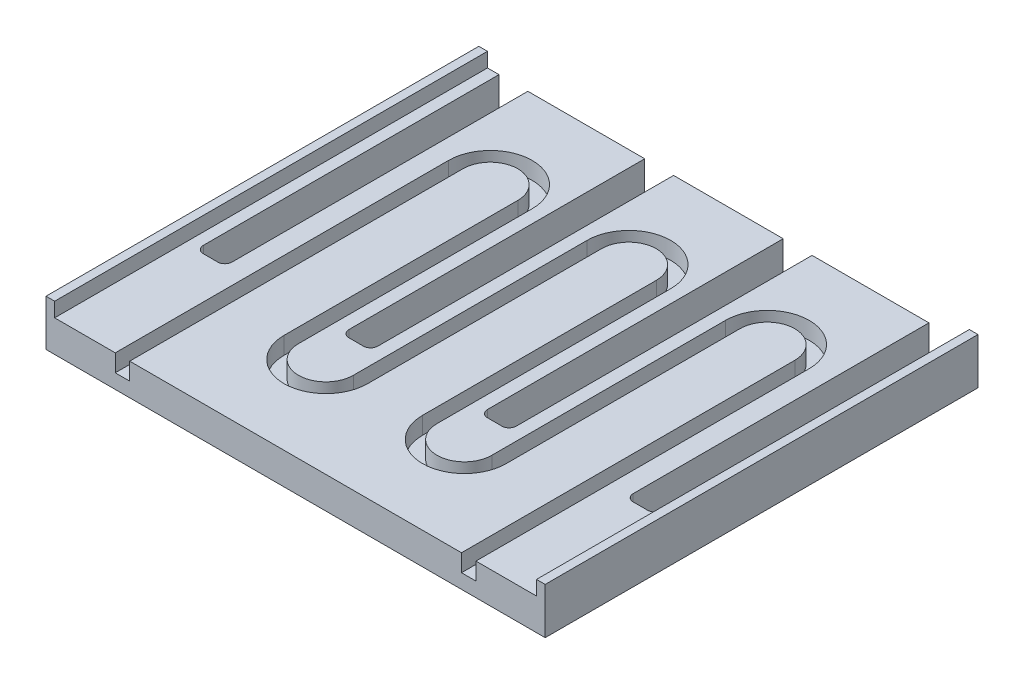
SolidWorks part; units mm, degrees
ref_plane "Спереди" through (0, 0, 0) normal (0, 0, 1) x (1, 0, 0)
ref_plane "Сверху" through (0, 0, 0) normal (0, 1, 0) x (1, 0, 0)
ref_plane "Справа" through (0, 0, 0) normal (1, 0, 0) x (0, 0, -1)
sketch "Подложка трубки" plane through (0, 0, 0) normal (0, 1, 0) x (1, 0, 0)
  line L0 (5.3073, 0.8937) -> (101.8191, 0.8937) construction
  line L1 (12, 0) -> (12, 50)
  line L2 (0, 0) -> (2.5, 0)
  line L3 (0, 0) -> (0, 50)
  line L4 (0, 50) -> (2.5, 50)
  line L5 (2.5, 0) -> (2.5, 50)
  line L6 (12, 0) -> (14.5, 0)
  line L7 (14.5, 0) -> (14.5, 50)
  line L8 (12, 50) -> (14.5, 50)
  line L9 (24, 0) -> (24, 50)
  line L10 (24, 0) -> (26.5, 0)
  line L11 (26.5, 0) -> (26.5, 50)
  line L12 (24, 50) -> (26.5, 50)
  line L13 (36, 0) -> (36, 50)
  line L14 (36, 0) -> (38.5, 0)
  line L15 (38.5, 0) -> (38.5, 50)
  line L16 (36, 50) -> (38.5, 50)
  line L17 (48, 0) -> (48, 50)
  line L18 (48, 0) -> (50.5, 0)
  line L19 (50.5, 0) -> (50.5, 50)
  line L20 (48, 50) -> (50.5, 50)
  line L21 (60, 0) -> (60, 50)
  line L22 (60, 0) -> (62.5, 0)
  line L23 (62.5, 0) -> (62.5, 50)
  line L24 (60, 50) -> (62.5, 50)
  line L25 (62.9198, 62.5) -> (-29.5124, 62.5) construction
  line L26 (0, 50) -> (14.5, 50)
  line L27 (0, 50) -> (0, 52.5)
  line L28 (0, 52.5) -> (14.5, 52.5)
  line L29 (14.5, 50) -> (14.5, 52.5)
  line L30 (24, 50) -> (38.5, 50)
  line L31 (24, 50) -> (24, 52.5)
  line L32 (24, 52.5) -> (38.5, 52.5)
  line L33 (38.5, 50) -> (38.5, 52.5)
  line L34 (48, 50) -> (62.5, 50)
  line L35 (48, 50) -> (48, 52.5)
  line L36 (48, 52.5) -> (62.5, 52.5)
  line L37 (62.5, 50) -> (62.5, 52.5)
  line L38 (12, 0) -> (26.5, 0)
  line L39 (12, 0) -> (12, -2.5)
  line L40 (12, -2.5) -> (26.5, -2.5)
  line L41 (26.5, 0) -> (26.5, -2.5)
  line L42 (36, 0) -> (50.5, 0)
  line L43 (36, 0) -> (36, -2.5)
  line L44 (36, -2.5) -> (50.5, -2.5)
  line L45 (50.5, 0) -> (50.5, -2.5)
  line L46 (0, 0) -> (2.5, 0)
  line L47 (0, 0) -> (0, -12.5)
  line L48 (0, -12.5) -> (2.5, -12.5)
  line L49 (2.5, 0) -> (2.5, -12.5)
  line L50 (60, 0) -> (62.5, 0)
  line L51 (60, 0) -> (60, -12.5)
  line L52 (60, -12.5) -> (62.5, -12.5)
  line L53 (62.5, 0) -> (62.5, -12.5)
  line L54 (-81.4744, -12.5) -> (67.6729, -12.5) construction
  line L55 (0, 62.7) -> (0, -70.5156) construction
  line L56 (26.25, -2.5) -> (26.25, -20) construction
  line L57 (-12, -12.5) -> (-12, 62.5)
  line L58 (74.5, -12.5) -> (74.5, 62.5) construction
  line L59 (62.5, 58.4344) -> (62.5, -75.5615) construction
  line L60 (-12, 62.5) -> (74.5, 62.5)
  line L61 (-12, 62.5) -> (-12, -12.5)
  line L62 (-12, -12.5) -> (74.5, -12.5)
  line L63 (74.5, 62.5) -> (74.5, -12.5)
  point P25 (0, -12.5)
  point P53 (74.5, 0.8937)
  point P55 (-12, 0.8937)
  point P60 (62.5, -12.5)
  point P64 (62.5, -12.5)
  dimension "D1" = 50
  dimension "D2" = 2.5
  dimension "D4" = 12
  dimension "D5" = 2.5
  dimension "D11" = 2.5
  dimension "D14" = 2.5
  dimension "D13" = 10
  dimension "D6" = 12
  dimension "D8" = 12
  dimension "D7" = 86.5
  dimension "D9" = 75
  dimension "D3" = 6
extrude "Бобышка-Вытянуть4" add sketch "Подложка трубки" along normal blind 5.5 contours L63 L60 L57 L62 L47 L3 L27 L28 L29 L7 L38 L9 L31 L32 L33 L15 L42 L17 L35 L36 L37 L23 L53 | L49 L62 L51 L21 L34 L19 L45 L44 L43 L13 L30 L11 L41 L40 L39 L1 L26 L5 region at (31.25, 0, -15.0747) region at (15.6449, 0, -25)
extrude "Бобышка-Вытянуть6" add sketch "Подложка трубки<9>" along normal blind 2.5 contours L49 L2 L47 L48 | L2 L5 L4 L3 | L41 L10 L38 L6 L39 L40 | L8 L1 L6 L7 | L12 L9 L10 L11 | L8 L29 L28 L27 L4 L26 | L16 L33 L32 L31 L12 L30 | L16 L13 L14 L15 | L45 L18 L42 L14 L43 L44 | L20 L17 L18 L19 | L24 L37 L36 L35 L20 L34 | L24 L21 L22 L23 | L51 L52 L53 L50 region at (13.25, 0, -25) region at (19.25, 0, 1.25) region at (7.25, 0, -51.25) region at (1.25, 0, -25) region at (25.25, 0, -25) region at (1.25, 0, 6.25) region at (31.25, 0, -51.25) region at (37.25, 0, -25) region at (61.25, 0, -25) region at (43.25, 0, 1.25) region at (55.25, 0, -51.25) region at (49.25, 0, -25)
sketch "Подложка трубки<9>" plane through (0, 0, 0) normal (0, 1, 0) x (1, 0, 0) same geometry as "Подложка трубки"
sketch "DS18B20" plane through (0, 5.5, 0) normal (0, 1, 0) x (1, 0, 0)
  line L0 (-12, 5) -> (74.5, 5)
  line L1 (-12, -12.5) -> (-12, 62.5) construction
  line L2 (74.5, 62.5) -> (74.5, -12.5) construction
  line L3 (14.5, 0) -> (24, 0) construction
  line L4 (-12, 16.3698) -> (0, 20)
  line L5 (0, 52.5) -> (0, -12.5) construction
  line L6 (14.5, 20) -> (24, 20)
  line L7 (14.5, 0) -> (14.5, 52.5) construction
  line L8 (24, 0) -> (24, 52.5) construction
  line L9 (38.5, 20) -> (48, 20)
  line L10 (38.5, 0) -> (38.5, 52.5) construction
  line L11 (48, 0) -> (48, 52.5) construction
  line L12 (62.5, 20) -> (74.5, 20)
  line L13 (62.5, -12.5) -> (62.5, 52.5) construction
  line L14 (62.5, -12.5) -> (62.5, 52.5) construction
  line L15 (-12, 62.5) -> (74.5, 62.5) construction
  line L16 (66, 62.5) -> (71, 62.5)
  line L17 (66, 62.5) -> (66, 10)
  line L18 (66, 10) -> (71, 10)
  line L19 (71, 62.5) -> (71, 10)
  line L20 (14.5, 0) -> (24, 0) construction
  line L21 (-8.5, 62.5) -> (-3.5, 62.5)
  line L22 (-8.5, 62.5) -> (-8.5, 10)
  line L23 (-8.5, 10) -> (-3.5, 10)
  line L24 (-3.5, 62.5) -> (-3.5, 10)
  line L25 (16.75, 62.5) -> (21.75, 62.5)
  line L26 (16.75, 62.5) -> (16.75, 10)
  line L27 (16.75, 10) -> (21.75, 10)
  line L28 (21.75, 62.5) -> (21.75, 10)
  line L30 (40.75, 62.5) -> (45.75, 62.5)
  line L31 (40.75, 62.5) -> (40.75, 10)
  line L32 (40.75, 10) -> (45.75, 10)
  line L33 (45.75, 62.5) -> (45.75, 10)
  line M3 (74.5, 62.5) -> (-12, 62.5)
  dimension "D4" = 12
  dimension "D1" = 5
  dimension "D6" = 5
  dimension "D7" = 9.5
  dimension "D8" = 2.25
  dimension "D2" = 2.25
  dimension "D3" = 3.5
  dimension "D5" = 3.5
  dimension "D9" = 10
extrude "Вырез-Вытянуть1" cut sketch "DS18B20" against normal blind 5 contours L24 L22 L4 M3 | L24 L4 L22 L23 | L28 L26 L6 M3 | L28 L6 L26 L27 | L33 L31 L9 M3 | L33 L9 L31 L32 | L19 L17 L12 M3 | L19 L12 L17 L18 region at (-6.0142, 5.5, -40.3403) region at (68.5, 5.5, -41.25) region at (43.25, 5.5, -41.25) region at (19.25, 5.5, -41.25) region at (-5.923, 5.5, -14.1041) region at (19.25, 5.5, -15) region at (43.25, 5.5, -15) region at (68.5, 5.5, -15)
sketch "Эскиз7" plane through (0, 5.5, 0) normal (0, 1, 0) x (1, 0, 0)
  line L0 (-12, -12.5) -> (0, -12.5) construction
  line L1 (-12, 62.5) -> (-10.5, 62.5)
  line L2 (-12, 62.5) -> (-12, -12.5)
  line L3 (-12, -12.5) -> (-10.5, -12.5)
  line L4 (-10.5, 62.5) -> (-10.5, -12.5)
  line L5 (62.5, -12.5) -> (74.5, -12.5) construction
  line L6 (74.5, 62.5) -> (73, 62.5)
  line L7 (74.5, 62.5) -> (74.5, -12.5)
  line L8 (74.5, -12.5) -> (73, -12.5)
  line L9 (73, 62.5) -> (73, -12.5)
  dimension "D1" = 1.5
extrude "Бобышка-Вытянуть8" add sketch "Эскиз7" along normal blind 2.5
fillet "Скругление1" 2 edges at (60, 4, -50) (50.5, 4, -50) type full round first side face at (60, 4, -18.75) second side face at (50.5, 4, -23.75) middle face at (55.25, 4, -50)
fillet "Скругление2" 2 edges at (62.5, 4, -52.5) (48, 4, -52.5) type full round first side face at (62.5, 4, -20) second side face at (48, 4, -26.25) middle face at (55.25, 4, -52.5)
fillet "Скругление3" 2 edges at (48, 4, 0) (38.5, 4, 0) type full round first side face at (48, 4, -22.625) second side face at (38.5, 4, -26.25) middle face at (43.25, 4, 0)
fillet "Скругление4" 2 edges at (50.5, 4, 2.5) (36, 4, 2.5) type full round first side face at (50.5, 4, -21.375) second side face at (36, 4, -23.75) middle face at (43.25, 4, 2.5)
fillet "Скругление5" 2 edges at (36, 4, -50) (26.5, 4, -50) type full round first side face at (36, 4, -27.375) second side face at (26.5, 4, -23.75) middle face at (31.25, 4, -50)
fillet "Скругление6" 2 edges at (38.5, 4, -52.5) (24, 4, -52.5) type full round first side face at (38.5, 4, -28.625) second side face at (24, 4, -26.25) middle face at (31.25, 4, -52.5)
fillet "Скругление7" 2 edges at (26.5, 4, 2.5) (12, 4, 2.5) type full round first side face at (26.5, 4, -21.375) second side face at (12, 4, -23.75) middle face at (19.25, 4, 2.5)
fillet "Скругление8" 2 edges at (14.5, 4, 0) (24, 4, 0) type full round first side face at (14.5, 4, -26.25) second side face at (24, 4, -22.625) middle face at (19.25, 4, 0)
fillet "Скругление9" 2 edges at (12, 4, -50) (2.5, 4, -50) type full round first side face at (12, 4, -27.375) second side face at (2.5, 4, -18.75) middle face at (7.25, 4, -50)
fillet "Скругление10" 2 edges at (14.5, 4, -52.5) (0, 4, -52.5) type full round first side face at (14.5, 4, -28.625) second side face at (0, 4, -20) middle face at (7.25, 4, -52.5)
fillet "Fillet1" radius 1.25 1 edges at (-8.5, 3, -10)
fillet "Fillet2" radius 1.25 7 edges at (-3.5, 3, -10) (16.75, 3, -10) (21.75, 3, -10) (40.75, 3, -10) (45.75, 3, -10) (71, 3, -10) (66, 3, -10)
equation "\"Tube\" = 2.5"
equation "\"D5@Подложка трубки\"=\"Tube\""
equation "\"D11@Подложка трубки\"=\"Tube\""
equation "\"D14@Подложка трубки\"=\"Tube\""
equation "\"D2@Подложка трубки\"=\"Tube\""
equation "\"Offset1\"= 12"
equation "\"D6@Подложка трубки\"=\"Offset1\""
equation "\"D8@Подложка трубки\"=\"Offset1\""
equation "\"Height\"= 3 + \"Tube\""
equation "\"D1@Бобышка-Вытянуть4\"=\"Height\""
equation "\"D1@Бобышка-Вытянуть6\"=\"Tube\""
equation "\"Pattern\" = 12"
equation "\"D4@Подложка трубки\"=\"Pattern\""
equation "\"Temp\" = 5"
equation "\"tempOffset\" = 5"
equation "\"D1@DS18B20\" = \"tempOffset\""
equation "\"D6@DS18B20\" = \"Temp\""
equation "\"D8@DS18B20\" =  ( \"D7@DS18B20\" - \"Temp\" )  / 2"
equation "\"D2@DS18B20\" =  ( \"D7@DS18B20\" - \"Temp\" )  / 2"
equation "\"D3@DS18B20\" =  ( \"D4@DS18B20\" - \"Temp\" )  / 2"
equation "\"D5@DS18B20\" =  ( \"D4@DS18B20\" - \"Temp\" )  / 2"
equation "\"D1@Вырез-Вытянуть1\"=\"Temp\""
